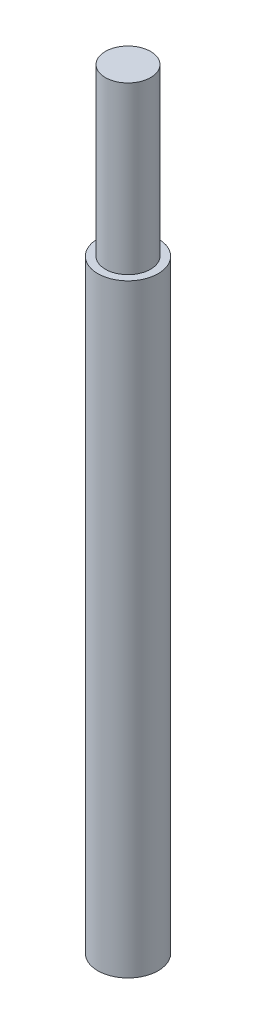
SolidWorks part; units mm, degrees
ref_plane "Front Plane" through (0, 0, 0) normal (0, 0, 1) x (1, 0, 0)
ref_plane "Top Plane" through (0, 0, 0) normal (0, 1, 0) x (1, 0, 0)
ref_plane "Right Plane" through (0, 0, 0) normal (1, 0, 0) x (0, 0, -1)
sketch "Sketch1" plane through (0, 0, 0) normal (0, 1, 0) x (1, 0, 0)
  circle A0 centre (0, 0) radius 4
  dimension "D1" = 8
extrude "Boss-Extrude1" add sketch "Sketch1" along normal blind 80
sketch "Sketch2" plane through (0, 80, 0) normal (0, 1, 0) x (1, 0, 0)
  circle A0 centre (0, 0) radius 3
  dimension "D1" = 6
extrude "Boss-Extrude2" add sketch "Sketch2" along normal blind 22
